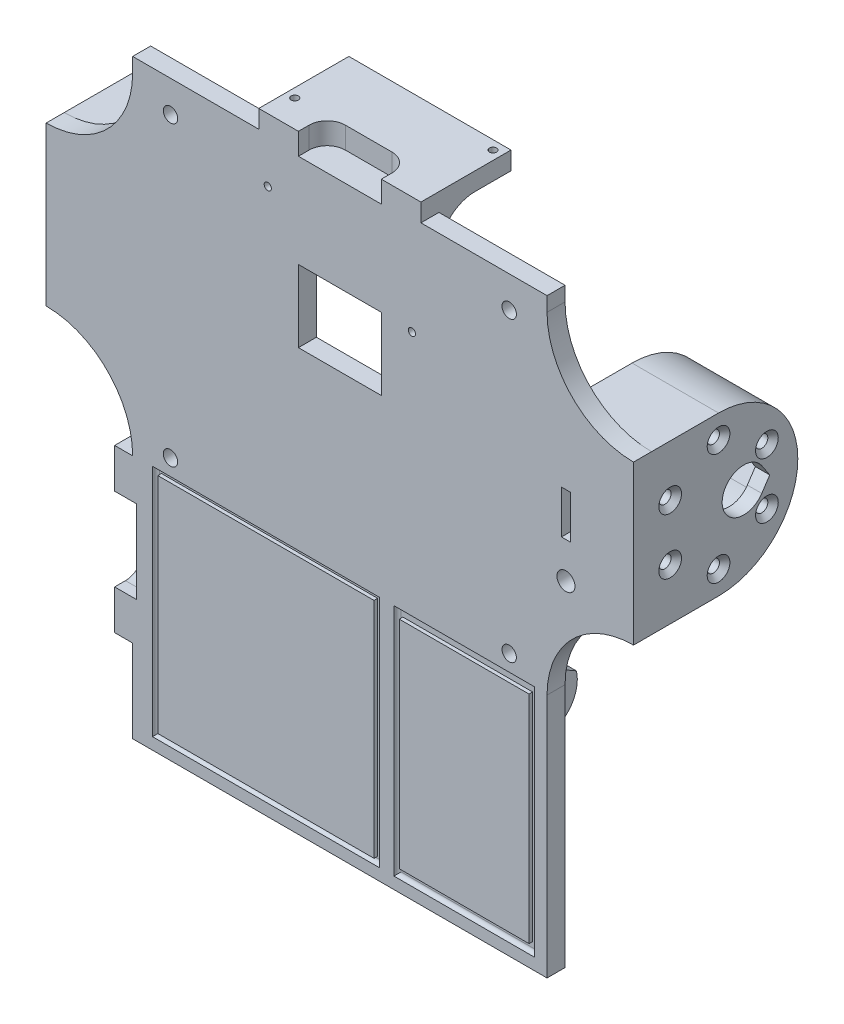
SolidWorks part; units mm, degrees
ref_plane "Front Plane" through (0, 0, 0) normal (0, 0, 1) x (1, 0, 0)
ref_plane "Top Plane" through (0, 0, 0) normal (0, 1, 0) x (1, 0, 0)
ref_plane "Right Plane" through (0, 0, 0) normal (1, 0, 0) x (0, 0, -1)
sketch "Sketch1" plane through (0, 0, 0) normal (0, 0, 1) x (1, 0, 0)
  line L0 (0, 0) -> (7, 5.25) construction
  line L1 (0, 0) -> (115, 0)
  line L2 (0, 0) -> (0, 100)
  line L3 (0, 100) -> (115, 100)
  line L4 (115, 0) -> (115, 100)
  line L5 (7, 94.75) -> (108, 94.75) construction
  line L6 (7, 94.75) -> (7, 5.25) construction
  line L7 (7, 5.25) -> (108, 5.25) construction
  line L8 (108, 94.75) -> (108, 5.25) construction
  line L9 (7, 94.75) -> (0, 100) construction
  line L10 (115, 100) -> (108, 94.75) construction
  line L11 (7, 94.75) -> (10.5, 91.25) construction
  line L12 (10.5, 91.25) -> (104.5, 91.25) construction
  line L13 (10.5, 91.25) -> (10.5, 8.75) construction
  line L14 (10.5, 8.75) -> (104.5, 8.75) construction
  line L15 (104.5, 91.25) -> (104.5, 8.75) construction
  line L16 (104.5, 91.25) -> (108, 94.75) construction
  line L17 (108, 5.25) -> (104.5, 8.75) construction
  line L18 (10.5, 8.75) -> (7, 5.25) construction
  circle A4 centre (10.5, 91.25) radius 2
  circle A5 centre (104.5, 91.25) radius 2
  circle A6 centre (104.5, 8.75) radius 2
  circle A7 centre (10.5, 8.75) radius 2
  dimension "D5" = 3.5
  dimension "D7" = 4
  dimension "D1" = 100
  dimension "D2" = 115
  dimension "D3" = 89.5
  dimension "D4" = 101
  dimension "D6" = 3.5
extrude "Boss-Extrude1" add sketch "Sketch1" along normal blind 5
sketch "Sketch2" plane through (0, 0, 5) normal (0, 0, 1) x (1, 0, 0)
  line L0 (115, 0) -> (115, 100) construction
  line L1 (0, 0) -> (115, 0)
  line L2 (0, 0) -> (0, -64)
  line L3 (0, -64) -> (115, -64)
  line L4 (115, 0) -> (115, -64)
  dimension "D1" = 64
extrude "Boss-Extrude2" add sketch "Sketch2" against normal up to surface (5 mm away) up to face at (106.5, 8.75, 0)
sketch "Sketch3" plane through (0, 0, 5) normal (0, 0, 1) x (1, 0, 0)
  line L0 (0, 100) -> (0, -64) construction
  line L1 (7, 2.75) -> (67, 2.75)
  line L2 (7, 2.75) -> (7, -59.25)
  line L3 (7, -59.25) -> (67, -59.25)
  line L4 (67, 2.75) -> (67, -59.25)
  line L5 (7, 2.75) -> (67, -59.25) construction
  line L6 (72.5, 4.25) -> (111.5, -60.75) construction
  line L7 (68.5, -60.75) -> (5.5, -60.75)
  line L8 (68.5, -60.75) -> (68.5, 4.25)
  line L9 (68.5, 4.25) -> (5.5, 4.25)
  line L10 (5.5, -60.75) -> (5.5, 4.25)
  line L11 (68.5, -60.75) -> (5.5, 4.25) construction
  line L12 (68.5, 4.25) -> (5.5, -60.75) construction
  line L13 (72.5, 4.25) -> (111.5, 4.25)
  line L14 (72.5, 4.25) -> (72.5, -60.75)
  line L15 (72.5, -60.75) -> (111.5, -60.75)
  line L16 (111.5, 4.25) -> (111.5, -60.75)
  line L18 (110, -58.25) -> (74, -58.25)
  line L19 (110, -58.25) -> (110, 1.75)
  line L20 (110, 1.75) -> (74, 1.75)
  line L21 (74, -58.25) -> (74, 1.75)
  line L22 (110, -58.25) -> (74, 1.75) construction
  line L23 (110, 1.75) -> (74, -58.25) construction
  circle A0 centre (10.5, 8.75) radius 2 construction
  point P8 (37, -28.25)
  point P17 (92, -28.25)
  point P18 (92, -28.25)
  dimension "D1" = 62
  dimension "D2" = 60
  dimension "D3" = 7
  dimension "D4" = 6
  dimension "D5" = 1.5
  dimension "D6" = 1.5
  dimension "D7" = 1.5
  dimension "D8" = 2.5
  dimension "D9" = 4
sketch "Sketch4" plane through (0, 100, 0) normal (0, 1, 0) x (1, 0, 0)
  line L0 (115, -5) -> (0, -5) construction
  line L2 (80, -5) -> (80, 20)
  line L3 (80, 20) -> (35, 20)
  line L4 (35, -5) -> (35, 20)
  line L5 (57.5, -5) -> (35, 20) construction
  line L6 (80, 20) -> (57.5, -5) construction
  line L7 (115, 0) -> (0, 0) construction
  line L8 (35, -5) -> (80, -5)
  line L9 (115, -5) -> (115, 0) construction
  point P0 (57.5, -5)
  dimension "D1" = 20
  dimension "D2" = 45
extrude "Boss-Extrude3" add sketch "Sketch4" along normal blind 5
sketch "Sketch5" plane through (0, 105, 0) normal (0, 1, 0) x (1, 0, 0)
  line L1 (0, 0) -> (115, 0) construction
  line L2 (35, 20) -> (35, -5) construction
  line L3 (80, -5) -> (80, 20) construction
  line L5 (80, 20) -> (35, 20) construction
  line L6 (35, 20) -> (46, -5) construction
  line L7 (46, 0) -> (69, 0) construction
  line L8 (46, 0) -> (46, -5) construction
  line L9 (46, -5) -> (69, -5) construction
  line L10 (69, 0) -> (69, -5) construction
  line L11 (69, -5) -> (80, 20) construction
  line L12 (35, -5) -> (80, -5) construction
  circle A0 centre (37.5, 2.5) radius 1
  circle A1 centre (77.5, 17.5) radius 1
  dimension "D5" = 2
  dimension "D1" = 2.5
  dimension "D2" = 2.5
  dimension "D3" = 2.5
  dimension "D4" = 2.5
  dimension "D6" = 5
  dimension "D7" = 23
extrude "Cut-Extrude2" cut sketch "Sketch5" against normal through all
fillet "Fillet1" radius 10 1 edges at (57.5, 100, 0)
sketch "Sketch6" plane through (0, 100, 0) normal (0, -1, 0) x (1, 0, 0)
  circle A0 centre (37.5, -2.5) radius 2.25
  dimension "D1" = 4.5
extrude "Cut-Extrude3" cut sketch "Sketch6" along normal through all
sketch "Sketch7" plane through (0, 105, 0) normal (0, 1, 0) x (1, 0, 0)
  line L1 (46, 3) -> (69, 3)
  line L2 (46, 3) -> (46, -5)
  line L3 (46, -5) -> (69, -5)
  line L4 (69, 3) -> (69, -5)
  dimension "D1" = 8
extrude "Cut-Extrude4" cut sketch "Sketch7" against normal blind 6
sketch "Sketch8" plane through (0, 0, 0) normal (0, 0, -1) x (-1, 0, 0)
  line L0 (-35, 90) -> (-35, 100) construction
  line L1 (-80, 90) -> (-35, 90) construction
  line L2 (-80, 90) -> (-80, 70) construction
  line L3 (-80, 70) -> (-35, 70) construction
  line L4 (-35, 90) -> (-35, 70) construction
  line L5 (-80, 70) -> (-69, 53) construction
  line L6 (-69, 73) -> (-46, 73)
  line L7 (-69, 73) -> (-69, 53)
  line L8 (-69, 53) -> (-46, 53)
  line L9 (-46, 73) -> (-46, 53)
  line L10 (-46, 53) -> (-35, 70) construction
  circle A0 centre (-37.5, 87.5) radius 1
  circle A1 centre (-77.5, 72.5) radius 1
  dimension "D2" = 2
  dimension "D3" = 2.5
  dimension "D5" = 2.5
  dimension "D1" = 20
  dimension "D4" = 2.5
  dimension "D6" = 2.5
  dimension "D7" = 23
  dimension "D8" = 20
  dimension "D9" = 3
extrude "Cut-Extrude5" cut sketch "Sketch8" against normal through all
ref_plane "Plane1" through (57.5, 0, 0) normal (-1, 0, 0) x (0, 0, 1)
sketch "Sketch9" plane through (115, 0, 0) normal (1, 0, 0) x (0, 0, -1)
  line L0 (0, 0) -> (0, 28) construction
  line L2 (0, 50) -> (18.6, 50) construction
  line L4 (18.6, 72) -> (0, 72)
  line L6 (18.6, 28) -> (0, 28)
  line L8 (-5, -64) -> (-5, 100) construction
  line L9 (0, 72) -> (-5, 72)
  line L11 (0, 28) -> (-5, 28)
  line L13 (-5, 72) -> (-5, 28)
  circle A0 centre (18.6, 50) radius 18.5
  arc A1 (18.6, 28) -> (18.6, 72) centre (18.6, 50) ccw
  dimension "D2" = 37
  dimension "D3" = 44
  dimension "D1" = 50
  dimension "D4" = 18.6
extrude "Boss-Extrude4" add sketch "Sketch9" along normal blind 20 separate body
sketch "Sketch10" plane through (135, 0, 0) normal (1, 0, 0) x (0, 0, -1)
  line L0 (18.6, 50) -> (34.1, 50) construction
  line L1 (32.0234, 57.75) -> (18.6, 50) construction
  line L2 (-5, 28) -> (18.6, 28) construction
  line L4 (18.6, 72) -> (-5, 72) construction
  line L5 (-5, 28) -> (18.6, 28)
  line L6 (-5, 72) -> (-5, 28)
  line L7 (18.6, 72) -> (-5, 72)
  circle A2 centre (18.6, 50) radius 18.5 construction
  circle A3 centre (18.6, 50) radius 18.5 construction
  circle A4 centre (25.6, 50) radius 6
  circle A5 centre (18.6, 50) radius 15.5 construction
  arc A6 (18.6, 28) -> (18.6, 72) centre (18.6, 50) ccw
  point P11 (32.0234, 57.75)
  point P17 (32.0234, 42.25)
  point P18 (18.6, 34.5)
  point P19 (5.1766, 42.25)
  point P20 (5.1766, 57.75)
  point P21 (18.6, 65.5)
  point P22 (18.6, 50)
  dimension "D1" = 12
  dimension "D3" = 31
  dimension "D2" = 7
  dimension "D4" = 30
  dimension "D5" = 6
extrude "Boss-Extrude5" add sketch "Sketch10" along normal blind 4
hole_wizard "CSK for M3 Flat Head Machine Screw1" positions "Sketch11" profile "Sketch12" countersink size "M3" standard "ANSI Metric" end condition through all
sketch "Sketch11" plane through (139, 0, 0) normal (1, 0, 0) x (0, 0, -1)
  point P0 (32.0234, 57.75)
  point P3 (18.6, 65.5)
  point P6 (5.1766, 57.75)
  point P9 (5.1766, 42.25)
  point P12 (18.6, 34.5)
  point P15 (32.0234, 42.25)
sketch "Sketch12" plane through (139, 57.75, -32.0234) normal (0, 1, 0) x (0, 0, -1)
  line L0 (0, 0) -> (0, 139)
  line L1 (0, 139) -> (1.7, 139)
  line L2 (1.7, 139) -> (1.7, 1.45)
  line L3 (1.7, 1.45) -> (3.15, 0)
  line L5 (3.15, 0) -> (0, 0)
  line L6 (-1.7, 1.45) -> (-3.15, 0) construction
  line L11 (0, -6.35) -> (0, 107.95) construction
  dimension "Thru Hole Dia." = 3.4
  dimension "Thru Hole Depth" = 139
  dimension "Near C'Sink Dia." = 6.3
  dimension "Near C'Sink Angle" = 90
mirror "Mirror10" about plane through (57.5, 0, 0) normal (-1, 0, 0) of "CSK for M3 Flat Head Machine Screw1", "Boss-Extrude5", "Boss-Extrude4"
sketch "Sketch15" plane through (0, 0, 0) normal (0, 0, -1) x (-1, 0, 0)
  line L0 (-139, 72) -> (-115, 72) construction
  line L1 (-115, -64) -> (-115, 100) construction
  line L2 (-139, 28) -> (-115, 28) construction
  line L3 (0, 28) -> (0, -64) construction
  line L4 (24, 28) -> (0, 28) construction
  line L5 (0, 100) -> (0, 72) construction
  line L6 (24, 72) -> (0, 72) construction
  line L7 (24, 72) -> (0, 72)
  line L8 (0, 72) -> (0, 96)
  line L9 (24, 28) -> (0, 28)
  line L10 (0, 28) -> (0, 4)
  line L11 (-115, 4) -> (-115, 28)
  line L12 (-115, 28) -> (-115, 72) construction
  line L13 (-115, 28) -> (-139, 28)
  line L14 (-115, 96) -> (-115, 72)
  line L15 (-115, 72) -> (-139, 72)
  arc A0 (-139, 72) -> (-115, 96) centre (-139, 96) ccw
  arc A1 (-115, 4) -> (-139, 28) centre (-139, 4) ccw
  arc A2 (0, 96) -> (24, 72) centre (24, 96) ccw
  arc A3 (24, 28) -> (0, 4) centre (24, 4) ccw
extrude "Boss-Extrude6" add sketch "Sketch15" against normal up to surface (5 mm away) up to face at (36.5, 87.5, 5)
ref_plane "Plane2" through (50.4, 0, 0) normal (-1, 0, 0) x (0, 0, 1)
sketch "Sketch16" plane through (50.4, 0, 0) normal (-1, 0, 0) x (0, 0, 1)
  line L0 (0, -9.5117) -> (-32.8318, -28.4672)
  line L1 (0, 4) -> (0, -64) construction
  line L2 (0, -9.5117) -> (0, -24.5117)
  line L3 (0, -24.5117) -> (-28.1738, -40.7779)
  line L4 (0, -17.0117) -> (-34.35, -36.8437) construction
  line L5 (-32.8318, -28.4672) -> (-43.5456, -34.6528)
  line L6 (-28.1738, -40.7779) -> (-37.0504, -45.9028)
  circle A0 centre (-34.35, -36.8437) radius 3.5
  arc A2 (-43.5456, -34.6528) -> (-37.0504, -45.9028) centre (-34.35, -36.8437) ccw
  dimension "D4" = 7
  dimension "D1" = 15
  dimension "D2" = 120
  dimension "D3" = 34.35
extrude "Boss-Extrude7" add sketch "Sketch16" along normal blind 10
mirror "Mirror11" about plane through (57.5, 0, 0) normal (-1, 0, 0) of "Boss-Extrude7"
fillet "Fillet3" radius 20 2 edges at (40.4, -17.0117, 0) (74.6, -17.0117, 0)
fillet "Fillet4" radius 5 4 edges at (35.4, -24.5117, 0) (79.6, -24.5117, 0) (35.4, -9.5117, 0) (79.6, -9.5117, 0)
sketch "Sketch19" plane through (0, 0, 0) normal (-1, 0, 0) x (0, 0, 1)
  line L0 (5, 4) -> (-20, 4)
  line L1 (-20, 4) -> (-20, -41)
  line L2 (5, -41) -> (-20, -41)
  line L3 (5.2881, -18.5) -> (-20, -41) construction
  line L4 (-20, 4) -> (5.2881, -18.5) construction
  line L5 (5, -41) -> (5, 4)
  line L8 (5, 4) -> (0, 4) construction
  line L9 (5, 4) -> (5, -64) construction
  point P0 (5.2881, -18.5)
  dimension "D1" = 45
  dimension "D2" = 25
extrude "Boss-Extrude9" add sketch "Sketch19" along normal blind 5
sketch "Sketch20" plane through (-5, 0, 0) normal (-1, 0, 0) x (0, 0, 1)
  line L0 (-20, 4) -> (-20, -41) construction
  line L1 (5, 4) -> (-20, 4) construction
  line L2 (0, -41) -> (0, -64) construction
  line L3 (-20, -41) -> (5, -41) construction
  circle A0 centre (-17.5, 1.5) radius 1
  circle A1 centre (-2.5, -38.5) radius 1
  dimension "D2" = 2.5
  dimension "D3" = 2
  dimension "D1" = 2.5
  dimension "D4" = 2.5
  dimension "D5" = 2.5
extrude "Cut-Extrude6" cut sketch "Sketch20" against normal up to surface (5 mm away) up to face at (0, -18.5, -10)
fillet "Fillet5" radius 10 1 edges at (0, -18.5, 0)
sketch "Sketch21" plane through (-5, 0, 0) normal (-1, 0, 0) x (0, 0, 1)
  line L0 (5, -41) -> (5, 4) construction
  line L1 (5, -7) -> (-3, -7)
  line L2 (5, -7) -> (5, -30)
  line L3 (5, -30) -> (-3, -30)
  line L4 (-3, -7) -> (-3, -30)
  line L5 (5, 4) -> (-3, -7) construction
  line L6 (5, -41) -> (-3, -30) construction
  dimension "D1" = 8
  dimension "D2" = 23
extrude "Cut-Extrude7" cut sketch "Sketch21" against normal blind 6
sketch "Sketch22" plane through (0, 0, 0) normal (1, 0, 0) x (0, 0, -1)
  circle A0 centre (2.5, -38.5) radius 2.25
  dimension "D1" = 4.5
extrude "Cut-Extrude8" cut sketch "Sketch22" along normal blind 15
sketch "Sketch23" plane through (0, 0, 5) normal (0, 0, 1) x (1, 0, 0)
  line L0 (139, 72) -> (147, 56) construction
  line L1 (117, 44) -> (117, 56) construction
  line L2 (117, 44) -> (147, 44) construction
  line L3 (147, 44) -> (147, 56) construction
  line L4 (117, 56) -> (147, 56) construction
  line L5 (139, 28) -> (147, 44) construction
  line L6 (119, 44) -> (120.25, 34) construction
  line L7 (139, 72) -> (139, 28) construction
  line L8 (121.5, 44) -> (121.5, 56)
  line L9 (121.5, 44) -> (119, 44)
  line L10 (119, 44) -> (119, 56)
  line L11 (121.5, 56) -> (119, 56)
  line L12 (120.25, 34) -> (121.5, 44) construction
  circle A0 centre (120.25, 34) radius 2.5
  point P16 (0, 0)
  dimension "D6" = 5
  dimension "D1" = 30
  dimension "D2" = 12
  dimension "D3" = 20
  dimension "D4" = 2.5
  dimension "D5" = 4.5
  dimension "D7" = 10
extrude "Cut-Extrude10" cut sketch "Sketch23" against normal blind 22
extrude "Cut-Extrude11" cut sketch "Sketch3" against normal blind 1
fillet "Fillet6" radius 1 8 edges at (37, -60.75, 4) (68.5, -28.25, 4) (37, 4.25, 4) (5.5, -28.25, 4) (92, -60.75, 4) (111.5, -28.25, 4) (92, 4.25, 4) (72.5, -28.25, 4)
fillet "Fillet7" radius 5 4 edges at (69, 102, -3) (46, 102, -3) (-2, -7, -3) (-2, -30, -3)
sketch "Sketch24" plane through (115, 0, 0) normal (-1, 0, 0) x (0, 0, 1)
  line L0 (-18.6, 50) -> (-55.3503, 50) construction
  line L1 (-35.057, 41.5491) -> (-39.3966, 50)
  line L2 (-39.3966, 50) -> (-35.057, 58.4509)
  circle A0 centre (-18.6, 50) radius 18.5 construction
  arc A1 (-35.057, 58.4509) -> (-35.057, 41.5491) centre (-18.6, 50) ccw
  dimension "D1" = 9.5
extrude "Cut-Extrude12" cut sketch "Sketch24" against normal up to surface (20 mm away) up to face at (135, 57.75, -33.7234)
sketch "Sketch25" plane through (135, 0, 0) normal (-1, 0, 0) x (0, 0, 1)
  line L0 (-25.6, 50) -> (-44.9333, 50) construction
  line L1 (-30.5923, 46.6718) -> (-32.8111, 50)
  line L6 (-32.8111, 50) -> (-30.5923, 53.3282)
  circle A0 centre (-25.6, 50) radius 6 construction
  arc A3 (-30.5923, 53.3282) -> (-30.5923, 46.6718) centre (-25.6, 50) ccw
  dimension "D2" = 4
extrude "Cut-Extrude13" cut sketch "Sketch25" against normal through all
mirror "Mirror14" about plane through (57.5, 0, 0) normal (-1, 0, 0) of "Cut-Extrude13"
sketch "Sketch26" plane through (0, 0, 0) normal (1, 0, 0) x (0, 0, -1)
  line L0 (35.057, 58.4509) -> (39.3966, 50) construction
  line L1 (39.3966, 50) -> (35.057, 41.5491) construction
  line L2 (35.057, 58.4509) -> (39.3966, 50)
  line L3 (39.3966, 50) -> (35.057, 41.5491)
  arc A0 (35.057, 41.5491) -> (35.057, 58.4509) centre (18.6, 50) ccw
extrude "Cut-Extrude14" cut sketch "Sketch26" against normal up to surface (20 mm away) up to face at (-20, 50, -37.1)
